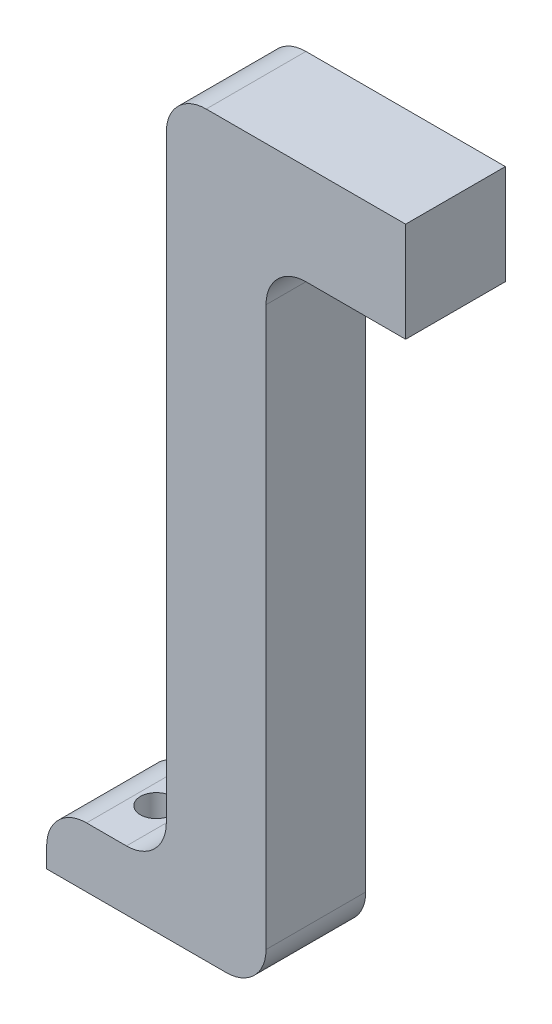
SolidWorks part; units mm, degrees
ref_plane "Front Plane" through (0, 0, 0) normal (0, 0, 1) x (1, 0, 0)
ref_plane "Top Plane" through (0, 0, 0) normal (0, 1, 0) x (1, 0, 0)
ref_plane "Right Plane" through (0, 0, 0) normal (1, 0, 0) x (0, 0, -1)
sketch "Sketch1" plane through (0, 0, 0) normal (0, 0, 1) x (1, 0, 0)
  line L0 (-1.4642, 0.25) -> (-1.4642, -7.75)
  line L5 (-1.4642, 0.25) -> (1.5358, 0.25)
  line L6 (-1.4642, 0.25) -> (-1.4642, 1.5)
  line L7 (-1.4642, 1.5) -> (1.5358, 1.5)
  line L8 (1.5358, 0.25) -> (1.5358, 1.5)
  line L9 (-1.4642, -7.75) -> (-2.9642, -7.75)
  line L10 (-1.4642, -7.75) -> (-1.4642, -7)
  line L11 (-1.4642, -7) -> (-2.9642, -7)
  line L12 (-2.9642, -7.75) -> (-2.9642, -7)
  line L13 (-1.4642, 0.25) -> (-0.2142, 0.25)
  line L14 (-1.4642, -7.75) -> (-0.2142, -7.75)
  line L15 (-0.2142, 0.25) -> (-0.2142, -7.75)
  dimension "D1" = 1.25
  dimension "D2" = 3
  dimension "D3" = 0
  dimension "D4" = 1.25
  dimension "D5" = 0.75
  dimension "D6" = 8
  dimension "D7" = 1.5
extrude "Boss-Extrude1" add sketch "Sketch1" along normal blind 0.625 and the other way blind 0.625 contours L5 L8 L7 L6 | L12 L9 L0 L11 | L13 L15 L14 L0 region at (0.0358, 0.875, 0) region at (-2.2142, -7.375, 0)
fillet "Fillet1" radius 0.5 5 edges at (-0.2142, 0.25, 0) (-1.4642, 1.5, 0) (-2.9642, -7, 0) (-0.2142, -7.75, 0) (-1.4642, -7, 0)
hole_wizard "Ø0.4 (0.4) Diameter Hole1" positions "Sketch2" profile "Sketch3" hole size "Ø0.4" standard "DIN" end condition through all
sketch "Sketch2" plane through (0, -7, 0) normal (0, 1, 0) x (1, 0, 0)
  line L0 (-1.4642, 0) -> (-2.9642, 0) construction
  point P0 (-2.2142, 0)
sketch "Sketch3" plane through (-2.2142, -7, 0) normal (1, 0, 0) x (0, 0, 1)
  line L0 (0, 0) -> (0, 0.75)
  line L1 (0, 0.75) -> (0.2, 0.75)
  line L2 (0.2, 0.75) -> (0.2, 0)
  line L5 (0.2, 0) -> (0, 0)
  line L11 (0, -6.35) -> (0, 107.95) construction
  dimension "Thru Hole Dia." = 0.4
  dimension "Thru Hole Depth" = 0.75
